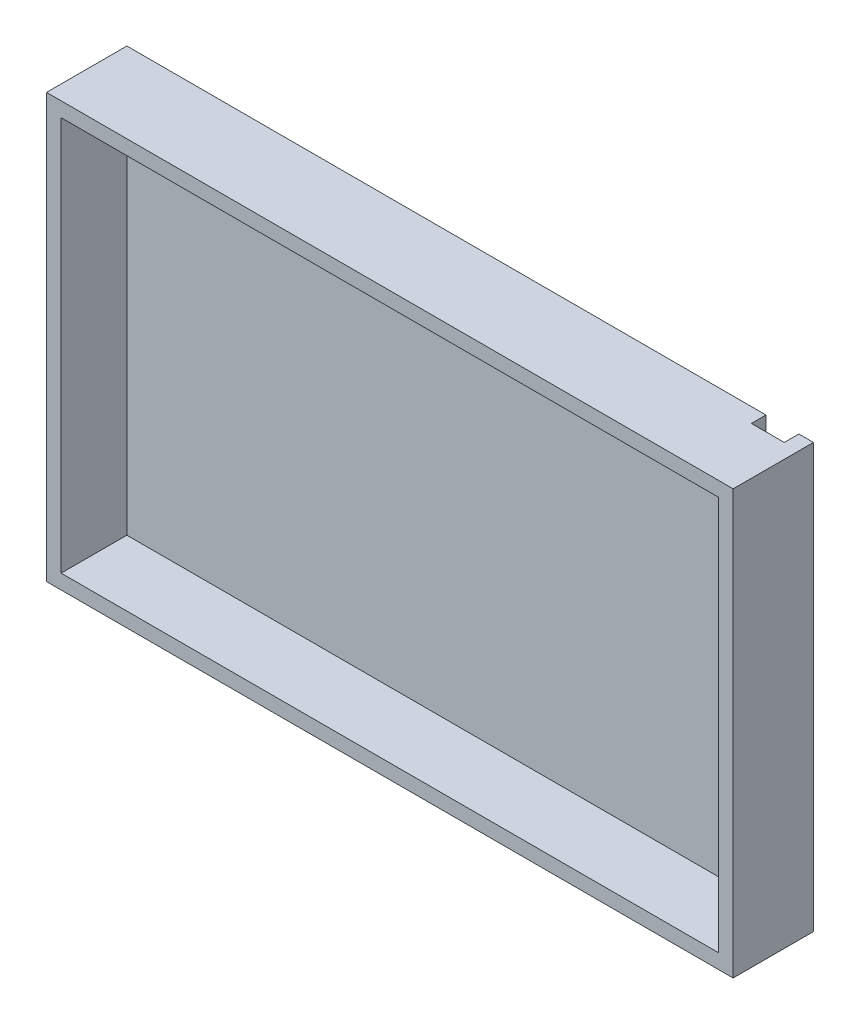
SolidWorks part; units mm, degrees
ref_plane "Front Plane" through (0, 0, 0) normal (0, 0, 1) x (1, 0, 0)
ref_plane "Top Plane" through (0, 0, 0) normal (0, 1, 0) x (1, 0, 0)
ref_plane "Right Plane" through (0, 0, 0) normal (1, 0, 0) x (0, 0, -1)
sketch "Sketch2" plane through (0, 0, 0) normal (0, 0, 1) x (1, 0, 0)
  line L1 (-47, 29) -> (47, 29)
  line L2 (-47, 29) -> (-47, -29)
  line L3 (-47, -29) -> (47, -29)
  line L4 (47, 29) -> (47, -29)
  line L5 (-47, 29) -> (47, -29) construction
  line L6 (-47, -29) -> (47, 29) construction
  point P0 (0, 0)
  dimension "D1" = 94
  dimension "D2" = 58
extrude "Boss-Extrude1" add sketch "Sketch2" along normal blind 11
sketch "Sketch3" plane through (0, 0, 11) normal (0, 0, 1) x (1, 0, 0)
  line L1 (-45, 27) -> (45, 27)
  line L2 (-45, 27) -> (-45, -27)
  line L3 (-45, -27) -> (45, -27)
  line L4 (45, 27) -> (45, -27)
  line L5 (-45, 27) -> (45, -27) construction
  line L6 (-45, -27) -> (45, 27) construction
  point P0 (0, 0)
  dimension "D1" = 90
  dimension "D2" = 54
extrude "Cut-Extrude1" cut sketch "Sketch3" against normal blind 9
sketch "Sketch5" plane through (0, 0, 0) normal (0, 0, -1) x (-1, 0, 0)
  line L1 (-47, 29) -> (47, 29) construction
  line L2 (-45, 29) -> (-45, -29)
  line L3 (47, -29) -> (-47, -29) construction
  line L6 (-45, 29) -> (-40.5, 29)
  line L8 (-45, -29) -> (-40.5, -29)
  line L9 (-40.5, 29) -> (-40.5, -29)
  line L10 (-45, 29) -> (-40.5, -29) construction
  line L11 (-45, -29) -> (-40.5, 29) construction
  point P11 (-42.75, 0)
  dimension "D1" = 58
  dimension "D2" = 4.5
extrude "Cut-Extrude2" cut sketch "Sketch5" against normal blind 2
